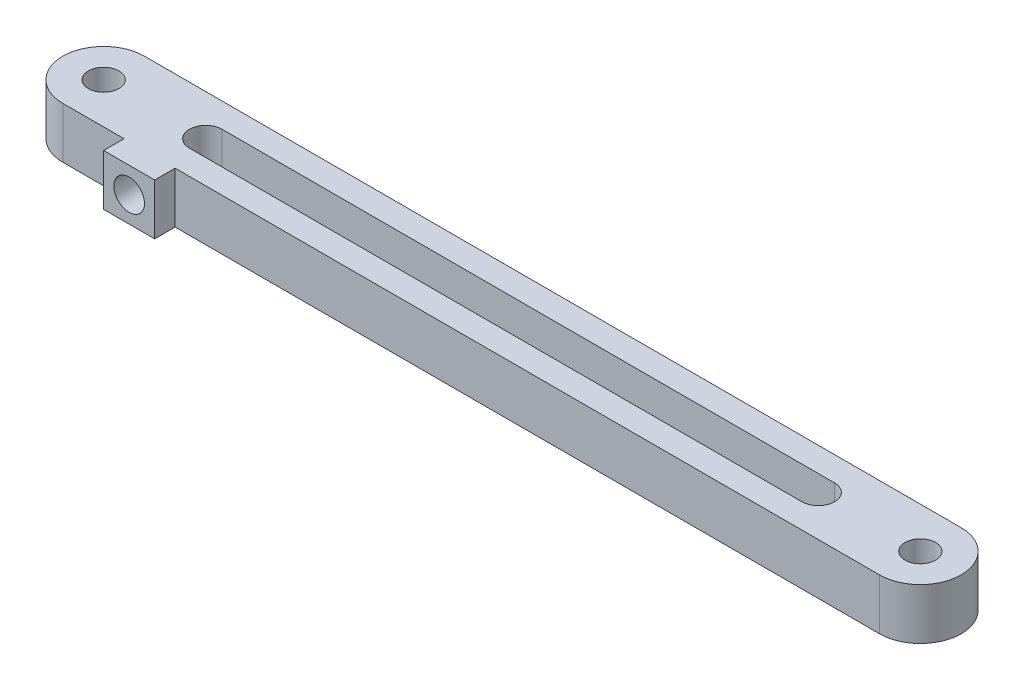
SolidWorks part; units mm, degrees
ref_plane "Front Plane" through (0, 0, 0) normal (0, 0, 1) x (1, 0, 0)
ref_plane "Top Plane" through (0, 0, 0) normal (0, 1, 0) x (1, 0, 0)
ref_plane "Right Plane" through (0, 0, 0) normal (1, 0, 0) x (0, 0, -1)
sketch "Sketch1" plane through (0, 0, 0) normal (0, 1, 0) x (1, 0, 0)
  line L0 (-40, 0) -> (40, 0) construction
  line L1 (-40, 4) -> (40, 4)
  line L2 (-40, -4) -> (40, -4)
  line L3 (-30, 0) -> (30, 0) construction
  line L4 (-30, 1.6) -> (30, 1.6)
  line L5 (-30, -1.6) -> (30, -1.6)
  arc A0 (-40, 4) -> (-40, -4) centre (-40, 0) ccw
  arc A1 (40, -4) -> (40, 4) centre (40, 0) ccw
  circle A2 centre (-40, 0) radius 1.5
  circle A3 centre (40, 0) radius 1.5
  arc A6 (-30, 1.6) -> (-30, -1.6) centre (-30, 0) ccw
  arc A7 (30, -1.6) -> (30, 1.6) centre (30, 0) ccw
  point P3 (0, 0)
  point P14 (0, 0)
  dimension "D2" = 4
  dimension "D3" = 3
  dimension "D1" = 80
  dimension "D4" = 3.2
  dimension "D5" = 60
extrude "Boss-Extrude1" add sketch "Sketch1" along normal blind 5 contours L2 A1 L1 A0 | A3 | A2 | L5 A7 L4 A6
sketch "Sketch2" plane through (0, 0, 4) normal (0, 0, 1) x (1, 0, 0)
  line L2 (-40, 5) -> (40, 5) construction
  line L3 (-34, 5) -> (-29, 5)
  line L4 (-34, 5) -> (-34, 0)
  line L5 (-34, 0) -> (-29, 0)
  line L6 (-29, 5) -> (-29, 0)
  line L7 (-40, 0) -> (40, 0) construction
  line L8 (-40, 5) -> (-40, 0) construction
  dimension "D1" = 6
  dimension "D2" = 5
extrude "Boss-Extrude2" add sketch "Sketch2" along normal blind 2
sketch "Sketch3" plane through (0, 0, 6) normal (0, 0, 1) x (1, 0, 0)
  line L0 (-34, 5) -> (-34, 0) construction
  line L1 (-29, 5) -> (-34, 5) construction
  circle A0 centre (-31.5, 2.5) radius 1.5
  dimension "D1" = 3
  dimension "D2" = 2.5
  dimension "D3" = 2.5
extrude "Cut-Extrude2" cut sketch "Sketch3" against normal blind 3
